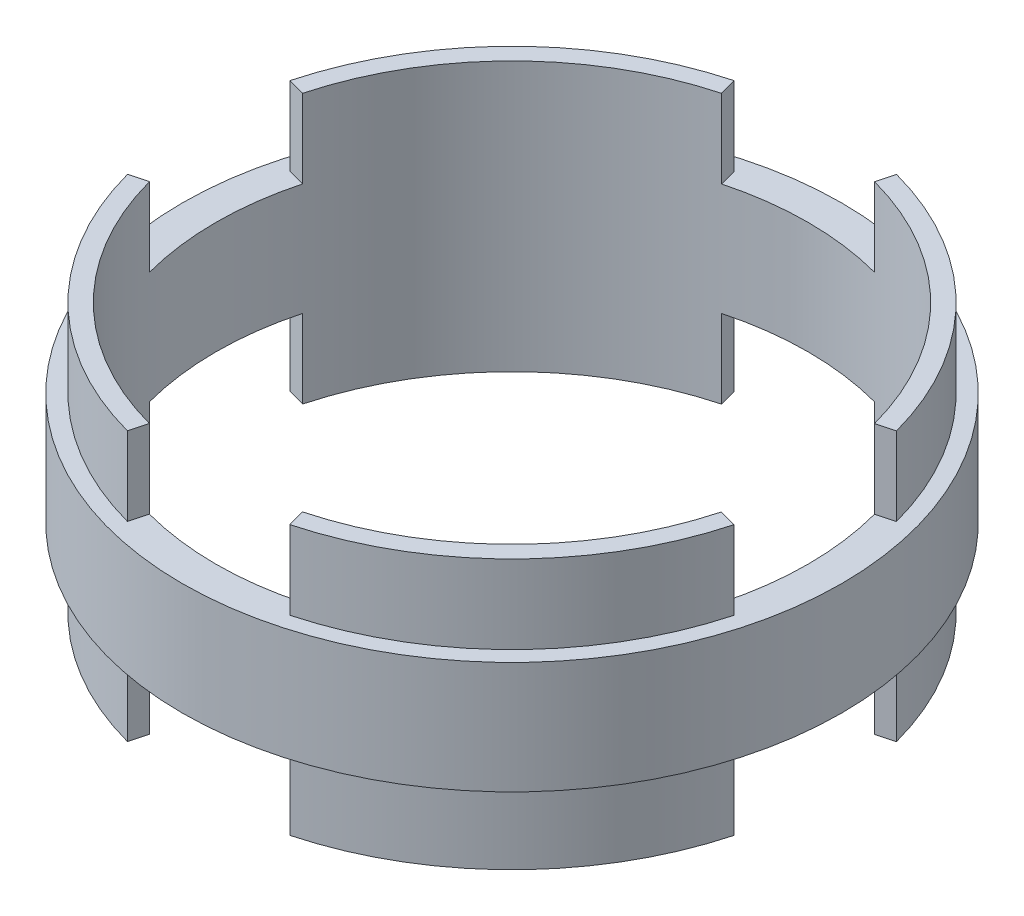
SolidWorks part; units mm, degrees
material "6061-T6 (SS)"
ref_plane "Front Plane" through (0, 0, 0) normal (0, 0, 1) x (1, 0, 0)
ref_plane "Top Plane" through (0, 0, 0) normal (0, 1, 0) x (1, 0, 0)
ref_plane "Right Plane" through (0, 0, 0) normal (1, 0, 0) x (0, 0, -1)
sketch "Sketch1" plane through (0, 0, 0) normal (0, 1, 0) x (1, 0, 0)
  circle A0 centre (0, 0) radius 93.345
  circle A1 centre (0, 0) radius 83.82
  dimension "D1" = 186.69
  dimension "D2" = 167.64
extrude "Boss-Extrude1" add sketch "Sketch1" along normal mid plane 31.75
sketch "Sketch2" plane through (0, 0, 0) normal (0, 1, 0) x (1, 0, 0)
  circle A0 centre (0, 0) radius 88.9
  circle A1 centre (0, 0) radius 83.82
  dimension "D1" = 177.8
  dimension "D2" = 167.64
extrude "Boss-Extrude2" add sketch "Sketch2" along normal mid plane 76.2
sketch "Sketch3" plane through (0, 0, 0) normal (0, 1, 0) x (1, 0, 0)
  line L0 (0, -116.3805) -> (0, 112.0878) construction
  line L1 (-120.9117, 0) -> (128.5432, 0) construction
  line L2 (0, 0) -> (-22.965, 85.8826)
  line L3 (0, 0) -> (23.009, 85.8708)
  circle A5 centre (0, 0) radius 88.9 construction
  arc A7 (-22.965, 85.8826) -> (23.009, 85.8708) centre (0, 0) cw
  dimension "D1" = 45.974
  dimension "D2" = 15
extrude "Cut-Extrude1" cut sketch "Sketch3" against normal mid plane 76.2
pattern_circular "CirPattern1" count 4 over 360 about axis through (0, 38.1, 0) along (0, -1, 0) of "Cut-Extrude1" reverse direction yes
sketch "Sketch4" plane through (0, 0, 0) normal (0, 1, 0) x (1, 0, 0)
  circle A0 centre (0, 0) radius 88.9
  circle A1 centre (0, 0) radius 83.82
extrude "Boss-Extrude3" add sketch "Sketch4" along normal mid plane 31.75
